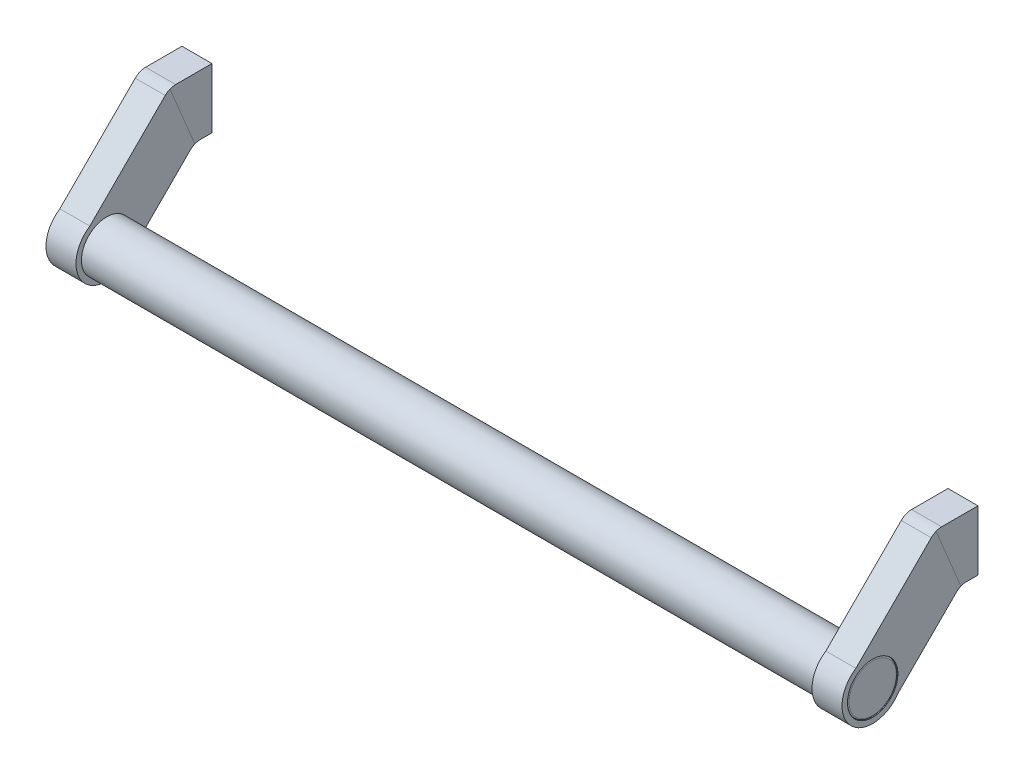
SolidWorks part; units mm, degrees
note: '?' marks a value the reader was unsure of.
ref_plane "Front Plane" through (0, 0, 0) normal (0, 0, 1) x (1, 0, 0)
ref_plane "Top Plane" through (0, 0, 0) normal (0, 1, 0) x (1, 0, 0)
ref_plane "Right Plane" through (0, 0, 0) normal (1, 0, 0) x (0, 0, -1)
sketch "Sketch1" plane through (0, 0, 0) normal (0, 0, 1) x (1, 0, 0)
  line L0 (-152.4, 0) -> (152.4, 0) construction
  line L2 (-158.369, 11.938) -> (-146.431, 11.938)
  line L3 (-158.369, 11.938) -> (-158.369, -11.938)
  line L4 (-158.369, -11.938) -> (-146.431, -11.938)
  line L5 (-146.431, 11.938) -> (-146.431, -11.938)
  line L6 (-158.369, 11.938) -> (-146.431, -11.938) construction
  line L7 (-158.369, -11.938) -> (-146.431, 11.938) construction
  line L8 (146.431, 11.938) -> (158.369, 11.938)
  line L9 (146.431, 11.938) -> (146.431, -11.938)
  line L10 (146.431, -11.938) -> (158.369, -11.938)
  line L11 (158.369, 11.938) -> (158.369, -11.938)
  line L12 (146.431, 11.938) -> (158.369, -11.938) construction
  line L13 (146.431, -11.938) -> (158.369, 11.938) construction
  circle A0 centre (-152.4, 0) radius 3.175
  circle A1 centre (152.4, 0) radius 3.175
  point P4 (0, 0)
  dimension "Center-to-Center Length" = 304.8
sketch "Sketch2" plane through (0, 0, 0) normal (1, 0, 0) x (0, 0, -1)
  line L0 (0, 0) -> (-11.938, 0)
  line L1 (-11.938, 0) -> (-41.91, -29.972)
  line L2 (0, -11.938) -> (0, 11.938) construction
  line L3 (0, 11.938) -> (0, -11.938) construction
  circle A0 centre (-41.91, -29.972) radius 10.033
  circle A1 centre (-41.91, -29.972) radius 12.192
  point P8 (0, 0)
  point P11 (-12.7, 0)
  dimension "D1" = 45
sketch "Sketch3" plane through (0, 0, 0) normal (0, 0, 1) x (1, 0, 0)
  line L4 (158.369, 11.938) -> (146.431, 11.938)
  line L5 (158.369, -11.938) -> (158.369, 11.938)
  line L6 (146.431, -11.938) -> (158.369, -11.938)
  line L7 (146.431, 11.938) -> (146.431, -11.938)
  line L8 (158.369, 11.938) -> (146.431, 11.938)
  line L9 (158.369, -11.938) -> (158.369, 11.938)
  line L10 (146.431, -11.938) -> (158.369, -11.938)
  line L11 (146.431, 11.938) -> (146.431, -11.938)
  line L12 (-146.431, 11.938) -> (-158.369, 11.938)
  line L13 (-146.431, -11.938) -> (-146.431, 11.938)
  line L14 (-158.369, -11.938) -> (-146.431, -11.938)
  line L15 (-158.369, 11.938) -> (-158.369, -11.938)
  line L16 (-146.431, 11.938) -> (-158.369, 11.938)
  line L17 (-146.431, -11.938) -> (-146.431, 11.938)
  line L18 (-158.369, -11.938) -> (-146.431, -11.938)
  line L19 (-158.369, 11.938) -> (-158.369, -11.938)
  dimension "D3" = 0
  dimension "D4" = 0
sketch "Sketch4" plane through (0, 0, 0) normal (1, 0, 0) x (0, 0, -1)
  line L2 (0, 0) -> (-11.938, 0) construction
  line L3 (-11.938, 0) -> (-41.91, -29.972) construction
  line L4 (0, 0) -> (-11.938, 0)
  line L5 (-11.938, 0) -> (-41.91, -29.972)
sweep "Handle Arm Sweep" add profiles "Sketch3" path "Sketch4"
sketch "Sketch5" plane through (0, 0, 0) normal (1, 0, 0) x (0, 0, -1)
  circle A1 centre (-41.91, -29.972) radius 12.192
  circle A2 centre (-41.91, -29.972) radius 12.192
  dimension "D1" = 0
extrude "Handle Arm Extrude 1" add sketch "Sketch5" against normal up to surface (11.938 mm away) from surface at -146.431 up to face at (-158.369, -14.986, 26.924) starting at face at (-146.431, -14.986, 26.924)
sketch "Sketch6" plane through (158.369, 0, 0) normal (1, 0, 0) x (0, 0, -1)
  circle A1 centre (-41.91, -29.972) radius 12.192
  circle A2 centre (-41.91, -29.972) radius 12.192
  dimension "D1" = 0
extrude "Handle Arm Extrude 2" add sketch "Sketch6" against normal up to surface (11.938 mm away) up to face at (146.431, -14.986, 26.924)
sketch "Sketch7" plane through (0, 0, 0) normal (1, 0, 0) x (0, 0, -1)
  circle A3 centre (-41.91, -29.972) radius 10.033
  circle A4 centre (-41.91, -29.972) radius 10.033
  dimension "D2" = 0
extrude "Handle Cut" cut sketch "Sketch7" against normal through all both and the other way through all
sketch "Sketch8" plane through (0, 0, 0) normal (1, 0, 0) x (0, 0, -1)
  circle A1 centre (-41.91, -29.972) radius 10.033
  circle A2 centre (-41.91, -29.972) radius 10.033
  dimension "D1" = 0
extrude "Handle Extrude" add sketch "Sketch8" along normal up to surface (158.369 mm away) and the other way up to surface (158.369 mm away) separate body
fillet "Handle Fillet" radius 0.635 2 edges at (-158.369, -29.972, 51.943) (158.369, -29.972, 31.877)
combine bodies "Handle Combine" operation type add bodies to combine 115 116 110
fillet "Handle Arm Fillet" radius 5.842 4 edges at (152.4, 11.938, 16.8829) (152.4, -11.938, 6.9931) (-152.4, -11.938, 6.9931) (-152.4, 11.938, 16.8829)
sketch "Sketch9" plane through (0, 0, 0) normal (0, 0, -1) x (-1, 0, 0)
  circle A0 centre (152.4, 0) radius 3.175 construction
  circle A1 centre (-152.4, 0) radius 3.175 construction
  circle A2 centre (152.4, 0) radius 3.175
  circle A3 centre (-152.4, 0) radius 3.175
extrude "Handle Thread Hole Cut" cut sketch "Sketch9" against normal up to vertex (12.7 mm away) up to point (0, 0, 12.7)
chamfer "Chamfer1" distance 0.635 angle 45 2 edges at (-155.575, 0, 0) (149.225, 0, 0)
sketch "Sketch10" plane through (0, 0, 0) normal (0, 0, 1) x (1, 0, 0)
  circle A1 centre (152.4, 0) radius 3.175 construction
  circle A3 centre (152.4, 0) radius 3.175
curve "Helix/Spiral1" pitch 1.27 height 13.97 turns 11 parameters "Pitch"=1.27
sketch "Sketch11" plane through (0, 0, 0) normal (0, 1, 0) x (1, 0, 0)
  line L0 (155.4375, -0.0794) -> (155.4375, 1.1906) construction
  line L1 (155.4375, 1.1906) -> (156.5374, 0.5556) construction
  line L2 (156.5374, 0.5556) -> (156.3999, 0.5556) construction
  line L3 (155.4375, -0.0794) -> (156.5374, 0.5556) construction
  line L4 (155.575, 0) -> (155.575, 1.1112) construction
  line L5 (156.3999, 0.4762) -> (156.3999, 0.635) construction
  line L6 (155.575, 0.5556) -> (155.4375, 0.5556) construction
  line L7 (155.5063, -0.0397) -> (155.5063, 1.1509) construction
  line L8 (146.431, 0) -> (158.369, 0) construction
  line L9 (155.5063, -0.0397) -> (155.5063, 1.1509)
  line L10 (155.5063, 1.1509) -> (156.3999, 0.635)
  line L11 (156.3999, 0.635) -> (156.3999, 0.4762)
  line L12 (156.3999, 0.4762) -> (155.5063, -0.0397)
  point P7 (155.575, 0.5556)
  point P10 (156.3999, 0.5556)
  point P16 (155.5063, 0.5556)
  dimension "D1" = 60
  dimension "D2" = 1.27
  dimension "D3" = 0.1588
sweep "Cut-Sweep1" cut profiles "Sketch11" path "Helix/Spiral1"
pattern_linear "LPattern1" count 2 spacing 304.8 along (1, 0, 0) of "Cut-Sweep1"
ref_axis "Center Axis 1" through (152.4, 0, 12.7) along (0, 0, -1)?
ref_axis "Center Axis 2" through (-152.4, 0, 12.7) along (0, 0, -1)?
ref_axis "Cemter Axis 3" through (146.431, -29.972, 41.91) along (-1, 0, 0)?
ref_plane "Contact Plane 1" through (0, 0, 0) normal (0, 0, 1) x (1, 0, 0)
equation "\"D3@Helix/Spiral1\"=\"Thread Depth (t)@Sketch2\"+\"Pitch@Helix/Spiral1\""
equation "\"D2@Sketch11\"=\"Pitch@Helix/Spiral1\""
equation "\"D3@Sketch11\"=\"Pitch@Helix/Spiral1\"/8"
equation "\"D3@LPattern1\"=\"Center-to-Center Length@Sketch1\""
